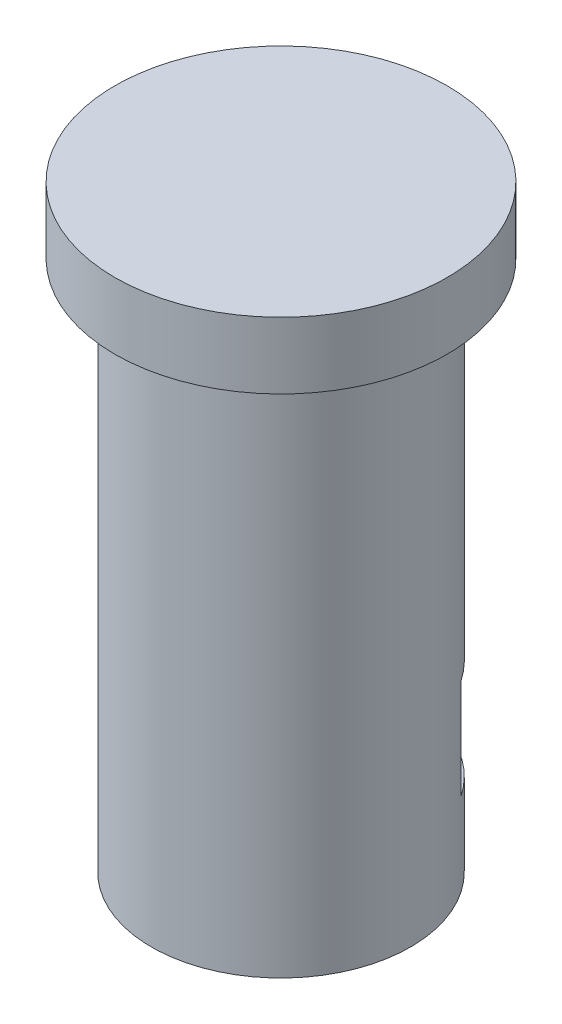
SolidWorks part; units mm, degrees
note: The reader was unsure of these and kept them because the rebuilt part matched: shared geometry of "Sketch3<5>".
ref_plane "Front Plane" through (0, 0, 0) normal (0, 0, 1) x (1, 0, 0)
ref_plane "Top Plane" through (0, 0, 0) normal (0, 1, 0) x (1, 0, 0)
ref_plane "Right Plane" through (0, 0, 0) normal (1, 0, 0) x (0, 0, -1)
sketch "Sketch1" plane through (0, 0, 0) normal (0, 1, 0) x (1, 0, 0)
  circle A0 centre (0, 0) radius 5
  circle A1 centre (0, 0) radius 6
  dimension "D1" = 10
  dimension "D2" = 1
extrude "Boss-Extrude1" add sketch "Sketch1" along normal blind 2 contours A0
sketch "Sketch4" plane through (0, 0, 0) normal (0, -1, 0) x (-1, 0, 0)
  circle A1 centre (0, 0) radius 3.9
  dimension "D2" = 7.8
extrude "Boss-Extrude2" add sketch "Sketch4" along normal blind 16
ref_plane "Plane1" through (0, -13.5, 0) normal (0, -1, 0) x (-1, 0, 0)
sketch "Sketch3" plane through (0, -13.5, 0) normal (0, 1, 0) x (1, 0, 0)
  line L1 (3.2259, -0.0375) -> (1.5805, 2.8125)
  line L2 (1.5805, 2.8125) -> (-1.7104, 2.8125)
  line L3 (-1.7104, 2.8125) -> (-3.3558, -0.0375)
  line L4 (-3.3558, -0.0375) -> (-1.7104, -2.8875)
  line L5 (-1.7104, -2.8875) -> (1.5805, -2.8875)
  line L6 (1.5805, -2.8875) -> (3.2259, -0.0375)
  circle A0 centre (-0.065, -0.0375) radius 2.85 construction
  circle A1 centre (-0.065, -0.0375) radius 1.7
  dimension "D1" = 5.7
  dimension "D2" = 3.4
extrude "Cut-Extrude4" cut sketch "Sketch3" along normal blind 3 contours L6 L5 L4 L3 L2 L1 A1
ref_plane "Plane2" through (0, 0, 0.0375) normal (0, 0, -1) x (-1, 0, 0)
extrude "Cut-Extrude5" cut sketch "Sketch3<5>" along normal blind 3 and the other way through all contours A1
sketch "Sketch3<5>" plane through (0, -13.5, 0) normal (0, 1, 0) x (1, 0, 0) same geometry as "Sketch3"
sketch "Sketch5" plane through (0, 0, 0.0375) normal (0, 0, 1) x (1, 0, 0)
  line L1 (-3.3558, -13.5) -> (3.2259, -13.5)
  line L2 (-3.3558, -13.5) -> (-3.3558, -10.5)
  line L3 (-3.3558, -10.5) -> (3.2259, -10.5)
  line L4 (3.2259, -13.5) -> (3.2259, -10.5)
extrude "Cut-Extrude6" cut sketch "Sketch5" against normal through all
